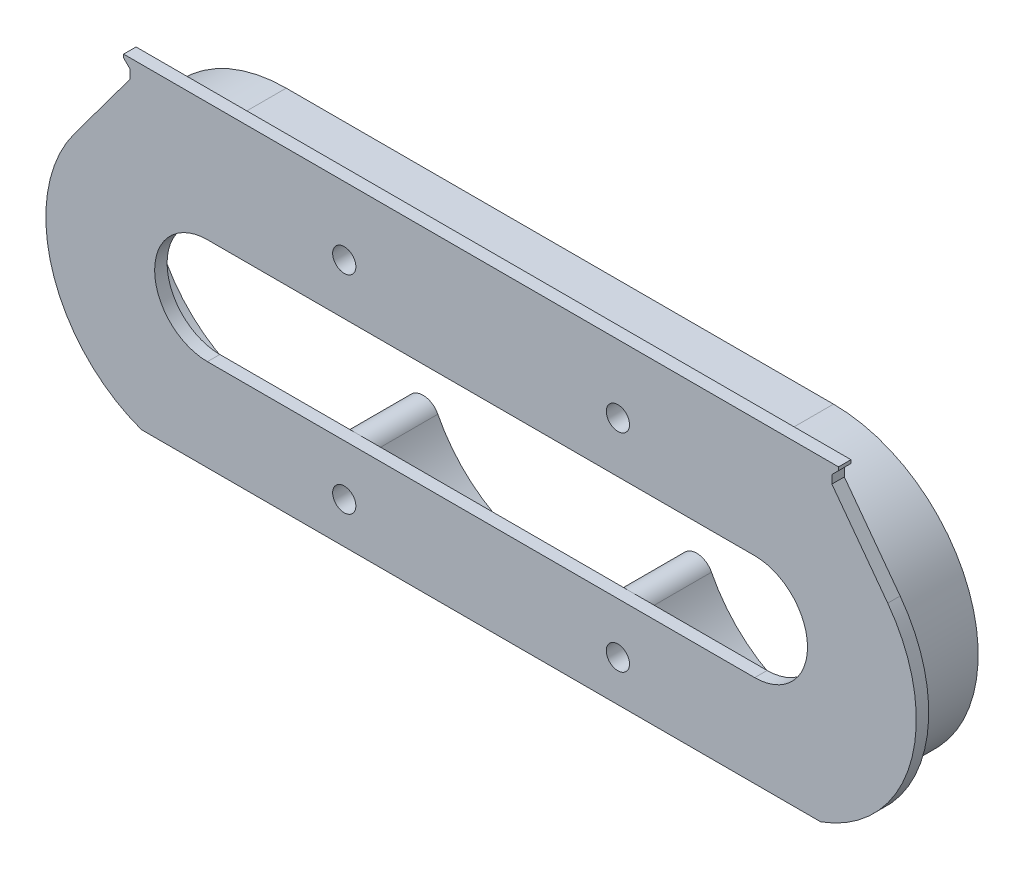
SolidWorks part; units mm, degrees
ref_plane "Front Plane" through (0, 0, 0) normal (0, 0, 1) x (1, 0, 0)
ref_plane "Top Plane" through (0, 0, 0) normal (0, 1, 0) x (1, 0, 0)
ref_plane "Right Plane" through (0, 0, 0) normal (1, 0, 0) x (0, 0, -1)
sketch "Sketch1" plane through (0, 0, 0) normal (0, 0, 1) x (1, 0, 0)
  line L2 (32.7948, -0.95) -> (98.7948, -0.95)
  line L3 (98.7948, 33.95) -> (32.7948, 33.95)
  line L4 (32.7948, -0.95) -> (98.7948, -0.95)
  line L5 (98.7948, 33.95) -> (32.7948, 33.95)
  circle A0 centre (49.2948, 29) radius 1.2 construction
  circle A1 centre (82.2948, 4) radius 1.2 construction
  arc A2 (32.7948, 33.95) -> (32.7948, -0.95) centre (32.7948, 16.5) ccw
  arc A3 (98.7948, -0.95) -> (98.7948, 33.95) centre (98.7948, 16.5) ccw
  arc A4 (32.7948, 33.95) -> (32.7948, -0.95) centre (32.7948, 16.5) ccw
  arc A5 (98.7948, -0.95) -> (98.7948, 33.95) centre (98.7948, 16.5) ccw
  circle A6 centre (49.2948, 4) radius 1.2 construction
  circle A7 centre (82.2948, 29) radius 1.2 construction
  circle A8 centre (82.2948, 29) radius 1.2
  circle A9 centre (49.2948, 4) radius 1.2
  circle A10 centre (82.2948, 4) radius 1.2
  circle A11 centre (49.2948, 29) radius 1.2
  arc A12 (47.511, 23.9621) -> (47.511, 9.0379) centre (32.7948, 16.5) ccw construction
  arc A13 (47.511, 23.9621) -> (51.0786, 23.9621) centre (49.2948, 24.8666) ccw construction
  arc A14 (80.511, 23.9621) -> (51.0786, 23.9621) centre (65.7948, 16.5) ccw construction
  arc A15 (51.0786, 9.0379) -> (47.511, 9.0379) centre (49.2948, 8.1334) ccw construction
  arc A16 (51.0786, 9.0379) -> (80.511, 9.0379) centre (65.7948, 16.5) ccw construction
  arc A17 (80.511, 23.9621) -> (84.0786, 23.9621) centre (82.2948, 24.8666) ccw construction
  arc A18 (84.0786, 9.0379) -> (84.0786, 23.9621) centre (98.7948, 16.5) ccw construction
  arc A19 (84.0786, 9.0379) -> (80.511, 9.0379) centre (82.2948, 8.1334) ccw construction
  arc A20 (84.0786, 9.0379) -> (80.511, 9.0379) centre (82.2948, 8.1334) ccw
  arc A21 (84.0786, 9.0379) -> (84.0786, 23.9621) centre (98.7948, 16.5) ccw
  arc A22 (80.511, 23.9621) -> (84.0786, 23.9621) centre (82.2948, 24.8666) ccw
  arc A23 (51.0786, 9.0379) -> (80.511, 9.0379) centre (65.7948, 16.5) ccw
  arc A24 (51.0786, 9.0379) -> (47.511, 9.0379) centre (49.2948, 8.1334) ccw
  arc A25 (80.511, 23.9621) -> (51.0786, 23.9621) centre (65.7948, 16.5) ccw
  arc A26 (47.511, 23.9621) -> (51.0786, 23.9621) centre (49.2948, 24.8666) ccw
  arc A27 (47.511, 23.9621) -> (47.511, 9.0379) centre (32.7948, 16.5) ccw
  dimension "D1" = 0
extrude "Boss-Extrude1" add sketch "Sketch1" along normal blind 8
sketch "Sketch2" plane through (0, 0, 8) normal (0, 0, 1) x (1, 0, 0)
  line L4 (30.8073, -2) -> (100.7824, -2)
  line L5 (114.8347, 25.9299) -> (108.1027, 35)
  line L6 (108.1027, 35) -> (108.1027, 36)
  line L7 (23.487, 35) -> (16.7549, 25.9299)
  line L8 (30.8073, -2) -> (100.7824, -2)
  line L9 (114.8347, 25.9299) -> (108.1027, 35)
  line L11 (23.487, 35) -> (16.7549, 25.9299)
  line L28 (108.1027, 35) -> (108.1027, 36)
  line L29 (108.1027, 36) -> (108.9027, 36.8)
  line L30 (108.1027, 36) -> (108.9027, 36.8)
  line L31 (108.9027, 36.8) -> (108.9027, 37.2)
  line L32 (108.9027, 36.8) -> (108.9027, 37.2)
  line L33 (108.9027, 37.2) -> (22.687, 37.2)
  line L34 (108.9027, 37.2) -> (22.687, 37.2)
  line L35 (22.687, 37.2) -> (22.687, 36.8)
  line L36 (22.687, 37.2) -> (22.687, 36.8)
  line L37 (22.687, 36.8) -> (23.487, 36)
  line L38 (22.687, 36.8) -> (23.487, 36)
  line L39 (23.487, 36) -> (23.487, 35)
  line L40 (23.487, 36) -> (23.487, 35)
  arc A2 (100.7824, -2) -> (114.8347, 25.9299) centre (100.7824, 15.5) ccw
  arc A3 (16.7549, 25.9299) -> (30.8073, -2) centre (30.8073, 15.5) ccw
  arc A4 (100.7824, -2) -> (114.8347, 25.9299) centre (100.7824, 15.5) ccw
  arc A5 (16.7549, 25.9299) -> (30.8073, -2) centre (30.8073, 15.5) ccw
  dimension "D1" = 0
extrude "Boss-Extrude2" add sketch "Sketch2" along normal blind 1.5
sketch "Sketch3" plane through (0, 0, 8) normal (0, 0, -1) x (-1, 0, 0)
  circle A0 centre (-49.2948, 4) radius 1.2 construction
  circle A1 centre (-49.2948, 29) radius 1.2 construction
  circle A2 centre (-82.2948, 4) radius 1.2 construction
  circle A3 centre (-82.2948, 29) radius 1.2 construction
  circle A4 centre (-49.2948, 4) radius 1.2
  circle A5 centre (-49.2948, 29) radius 1.2
  circle A6 centre (-82.2948, 4) radius 1.2
  circle A7 centre (-82.2948, 29) radius 1.2
  circle A8 centre (-49.2948, 29) radius 1.4
  circle A9 centre (-49.2948, 4) radius 1.4
  circle A10 centre (-82.2948, 4) radius 1.4
  circle A11 centre (-82.2948, 29) radius 1.4
  dimension "D1" = 0.2
  dimension "D2" = 0.2
extrude "Cut-Extrude1" cut sketch "Sketch3" against normal through all both and the other way through all contours A8 | A9 | A10 | A11
sketch "Sketch4" plane through (0, 0, 8) normal (0, 0, -1) x (-1, 0, 0)
  line L0 (-98.7948, 16.5) -> (-32.7948, 16.5) construction
  line L1 (-98.7948, 22.8666) -> (-32.7948, 22.8666)
  line L2 (-98.7948, 10.1334) -> (-32.7948, 10.1334)
  arc A0 (-98.7948, 22.8666) -> (-98.7948, 10.1334) centre (-98.7948, 16.5) ccw
  arc A1 (-32.7948, 10.1334) -> (-32.7948, 22.8666) centre (-32.7948, 16.5) ccw
  arc A2 (-80.511, 9.0379) -> (-84.0786, 9.0379) centre (-82.2948, 8.1334) ccw construction
  point P4 (-65.7948, 16.5)
extrude "Cut-Extrude2" cut sketch "Sketch4" against normal through all
sketch "Sketch5" plane through (0, 0, 8) normal (0, 0, -1) x (-1, 0, 0)
  line L0 (-32.7948, -0.95) -> (-98.7948, -0.95) construction
  line L1 (-12.434, -6.9663) -> (-129.7059, -6.9663)
  line L2 (-12.434, -6.9663) -> (-12.434, -0.95)
  line L3 (-12.434, -0.95) -> (-129.7059, -0.95)
  line L4 (-129.7059, -6.9663) -> (-129.7059, -0.95)
extrude "Cut-Extrude3" cut sketch "Sketch5" against normal through all
